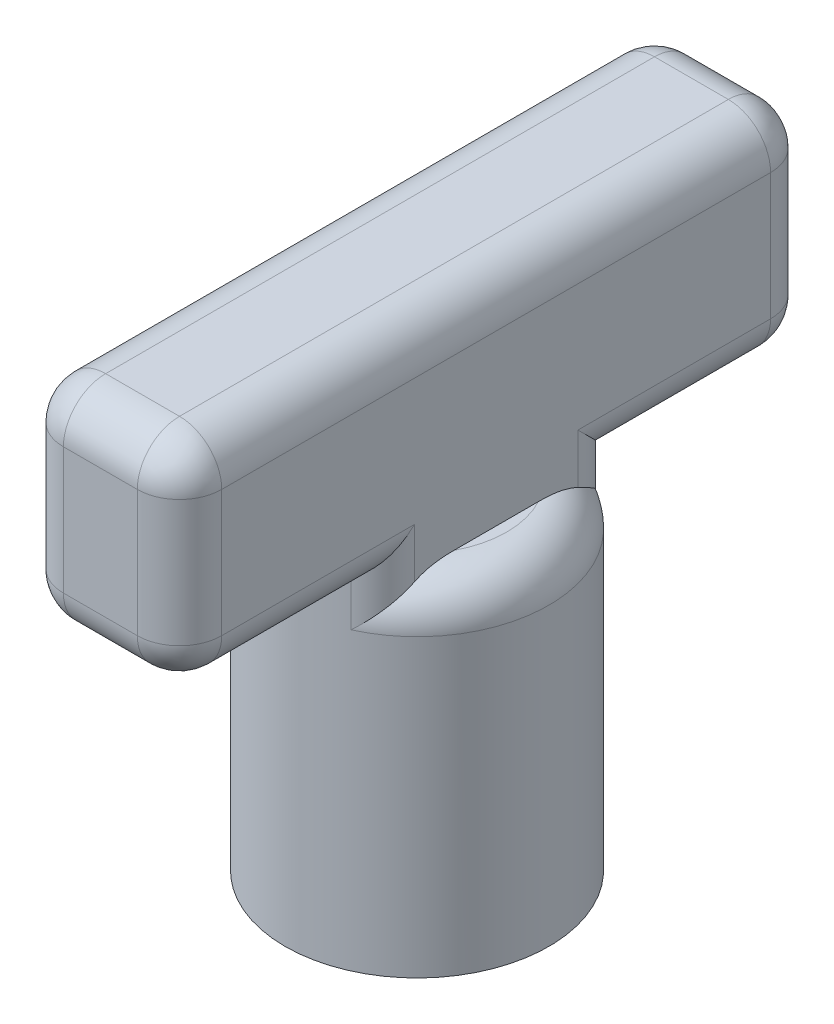
SolidWorks part; units mm, degrees
ref_plane "Front Plane" through (0, 0, 0) normal (0, 0, 1) x (1, 0, 0)
ref_plane "Top Plane" through (0, 0, 0) normal (0, 1, 0) x (1, 0, 0)
ref_plane "Right Plane" through (0, 0, 0) normal (1, 0, 0) x (0, 0, -1)
sketch "Sketch1" plane through (0, 0, 0) normal (0, 1, 0) x (1, 0, 0)
  circle A0 centre (0, 0) radius 2.5
  circle A1 centre (0, 0) radius 6.25
  dimension "D1" = 5
  dimension "D2" = 12.5
extrude "Boss-Extrude1" add sketch "Sketch1" along normal blind 5
sketch "Sketch2" plane through (0, 5, 0) normal (0, 1, 0) x (1, 0, 0)
  circle A1 centre (0, 0) radius 6.25
  circle A2 centre (0, 0) radius 6.25
  dimension "D1" = 0
extrude "Boss-Extrude2" add sketch "Sketch2" along normal blind 11
sketch "Sketch3" plane through (0, 16, 0) normal (0, 1, 0) x (1, 0, 0)
  line L1 (-3.75, 15) -> (3.75, 15)
  line L2 (-3.75, 15) -> (-3.75, -15)
  line L3 (-3.75, -15) -> (3.75, -15)
  line L4 (3.75, 15) -> (3.75, -15)
  line L5 (-3.75, 15) -> (3.75, -15) construction
  line L6 (-3.75, -15) -> (3.75, 15) construction
  point P0 (0, 0)
  dimension "D1" = 7.5
  dimension "D2" = 30
extrude "Boss-Extrude3" add sketch "Sketch3" along normal blind 10
fillet "Fillet1" radius 2 2 edges at (-6.25, 16, 0) (6.25, 16, 0)
fillet "Fillet2" radius 2 18 edges at (-3.75, 16, -10) (-3.75, 16, 10) (-3.75, 15, 5) (-3.75, 15, -5) (0, 16, -15) (-3.75, 21, -15) (3.75, 16, 10) (3.75, 21, -15) (3.75, 16, -10) (3.75, 15, -5) (3.75, 15, 5) (0, 16, 15) (-3.75, 21, 15) (3.75, 21, 15) (0, 26, 15) (-3.75, 26, 0) (0, 26, -15) (3.75, 26, 0)
